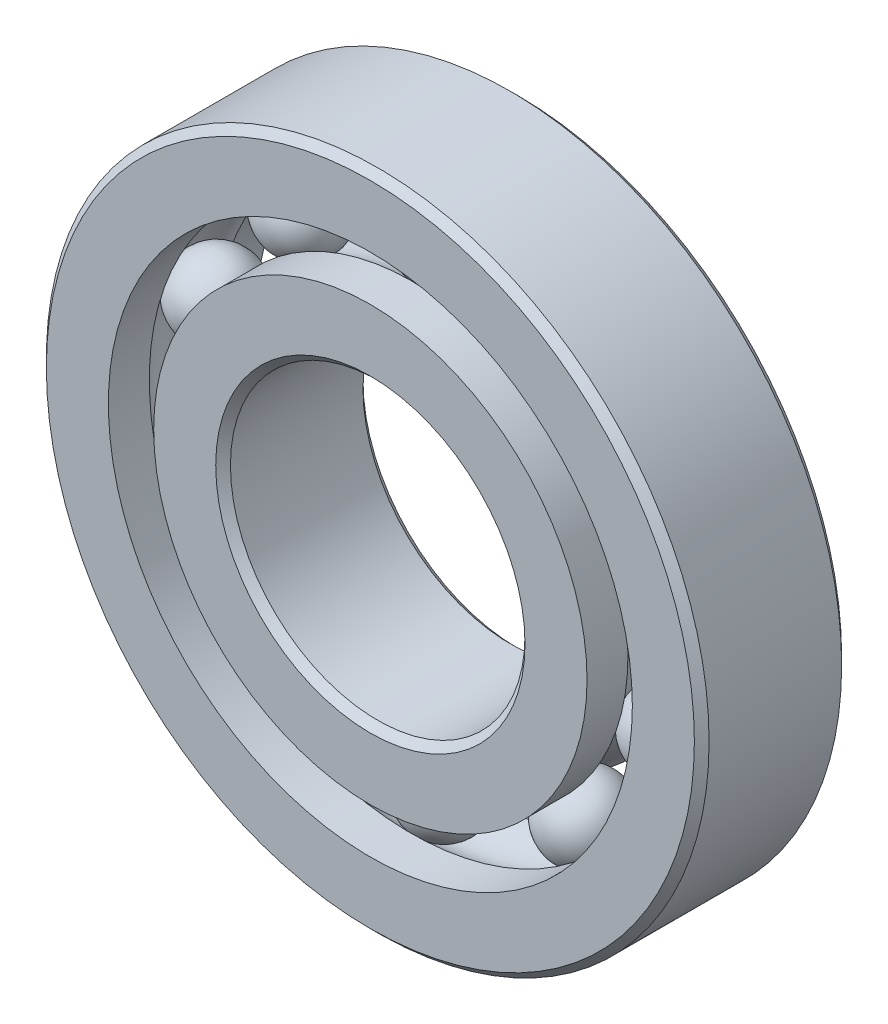
SolidWorks part; units mm, degrees
material "AISI 316 Stainless Steel Sheet (SS)"
ref_plane "Front Plane" through (0, 0, 0) normal (0, 0, 1) x (1, 0, 0)
ref_plane "Top Plane" through (0, 0, 0) normal (0, 1, 0) x (1, 0, 0)
ref_plane "Right Plane" through (0, 0, 0) normal (1, 0, 0) x (0, 0, -1)
sketch "Sketch1" plane through (0, 0, 0) normal (1, 0, 0) x (0, 0, -1)
  line L0 (-3.175, 0) -> (3.175, 0) construction
  line L1 (0, 14.2875) -> (0, -14.2875) construction
  line L2 (2.8575, 14.2875) -> (-2.8575, 14.2875)
  line L3 (-2.8575, 14.2875) -> (-3.175, 13.97)
  line L4 (-3.175, 13.97) -> (-3.175, 11.2957)
  line L5 (-3.175, 11.2957) -> (-1.4111, 11.2957)
  line L6 (3.175, 11.2957) -> (1.4111, 11.2957)
  line L7 (3.175, 13.97) -> (3.175, 11.2957)
  line L8 (2.8575, 14.2875) -> (3.175, 13.97)
  line L9 (0, 14.2875) -> (0, 10.3187) construction
  line L10 (0, 10.3187) -> (0, 6.35) construction
  arc A0 (-1.4111, 11.2957) -> (1.4111, 11.2957) centre (0, 10.3187) cw
  point P14 (0, 6.35)
  dimension "Width" = 6.35
  dimension "OD" = 28.575
  dimension "D1" = 45
  dimension "D2" = 0.3175
  dimension "Shaft Dia" = 12.7
  dimension "D3" = 2.8222
  dimension "D4" = 0.9769
revolve "Revolve1" add sketch "Sketch1" angle 360 about L0
sketch "Sketch3" plane through (0, 0, 0) normal (1, 0, 0) x (0, 0, -1)
  line L0 (-3.175, 9.3418) -> (-1.4111, 9.3418)
  line L1 (0, 14.2875) -> (0, -14.2875) construction
  line L2 (-3.175, 13.97) -> (-3.175, 11.2957) construction
  line L3 (-3.175, 9.3418) -> (-3.175, 6.6675)
  line L4 (-2.8575, 14.2875) -> (-3.175, 13.97) construction
  line L5 (-3.175, 6.6675) -> (-2.8575, 6.35)
  line L6 (-2.8575, 6.35) -> (2.8575, 6.35)
  line L7 (2.8575, 14.2875) -> (2.8575, -14.2875) construction
  line L8 (2.8575, 6.35) -> (3.175, 6.6675)
  line L9 (3.175, -13.97) -> (3.175, 13.97) construction
  line L10 (3.175, 6.6675) -> (3.175, 9.3418)
  line L11 (3.175, 9.3418) -> (1.4111, 9.3418)
  line L13 (2.8575, 14.2875) -> (3.175, 13.97) construction
  arc A0 (1.4111, 11.2957) -> (-1.4111, 11.2957) centre (0, 10.3187) ccw construction
  arc A1 (1.4111, 9.3418) -> (-1.4111, 9.3418) centre (0, 10.3187) cw
revolve "Revolve3" add sketch "Sketch3" angle 360 about L0
sketch "Sketch4" plane through (0, 0, 0) normal (1, 0, 0) x (0, 0, -1)
  line L0 (-1.7163, 10.3187) -> (1.7163, 10.3187)
  arc A2 (-1.7163, 10.3187) -> (1.7163, 10.3187) centre (0, 10.3187) cw
  arc A3 (1.4111, 11.2957) -> (-1.4111, 11.2957) centre (0, 10.3187) ccw construction
revolve "Revolve4" add sketch "Sketch4" angle 360 about L0
ref_axis "Axis1" through (0, 0, -3.175) along (0, 0, 1)
pattern_circular "CirPattern1" count 10 every 36 about axis through (0, 0, -3.175) along (0, 0, 1) of bodies 104
sketch "Sketch5" plane through (0, 0, 0) normal (1, 0, 0) x (0, 0, -1)
  line L0 (-3.175, 11.2957) -> (-1.4111, 11.2957) construction
  line L1 (-3.0162, 11.2957) -> (-1.7163, 11.2957)
  line L2 (-3.0162, 11.2957) -> (-3.0162, 9.3418)
  line L3 (-3.0162, 9.3418) -> (-1.7163, 9.3418)
  line L4 (-1.7163, 11.2957) -> (-1.7163, 9.3418)
  line L5 (-3.175, 9.3418) -> (-1.4111, 9.3418) construction
  line L6 (3.175, 11.2957) -> (1.4111, 11.2957) construction
  line L7 (3.0163, 11.2957) -> (1.7163, 11.2957)
  line L8 (3.0163, 11.2957) -> (3.0163, 9.3418)
  line L9 (3.0163, 9.3418) -> (1.7163, 9.3418)
  line L10 (1.7163, 11.2957) -> (1.7163, 9.3418)
  line L11 (3.175, 9.3418) -> (1.4111, 9.3418) construction
  line L12 (-2.8575, 14.2875) -> (-3.175, 13.97) construction
  point P18 (-3.0163, 14.1287)
revolve "Revolve5" [suppressed] add sketch "Sketch5" angle 360 about L0
equation "\"D2@Sketch1\" = \"Width@Sketch1\"*.05"
equation "\"D3@Sketch1\" = \"Width@Sketch1\"/2.25"
equation "\"D4@Sketch1\" = (((\"OD@Sketch1\"-\"Width@Sketch1\")/2)/3.25)/3.5"
equation "\"D2@CirPattern1\" = 360/\"Balls@CirPattern1\""
